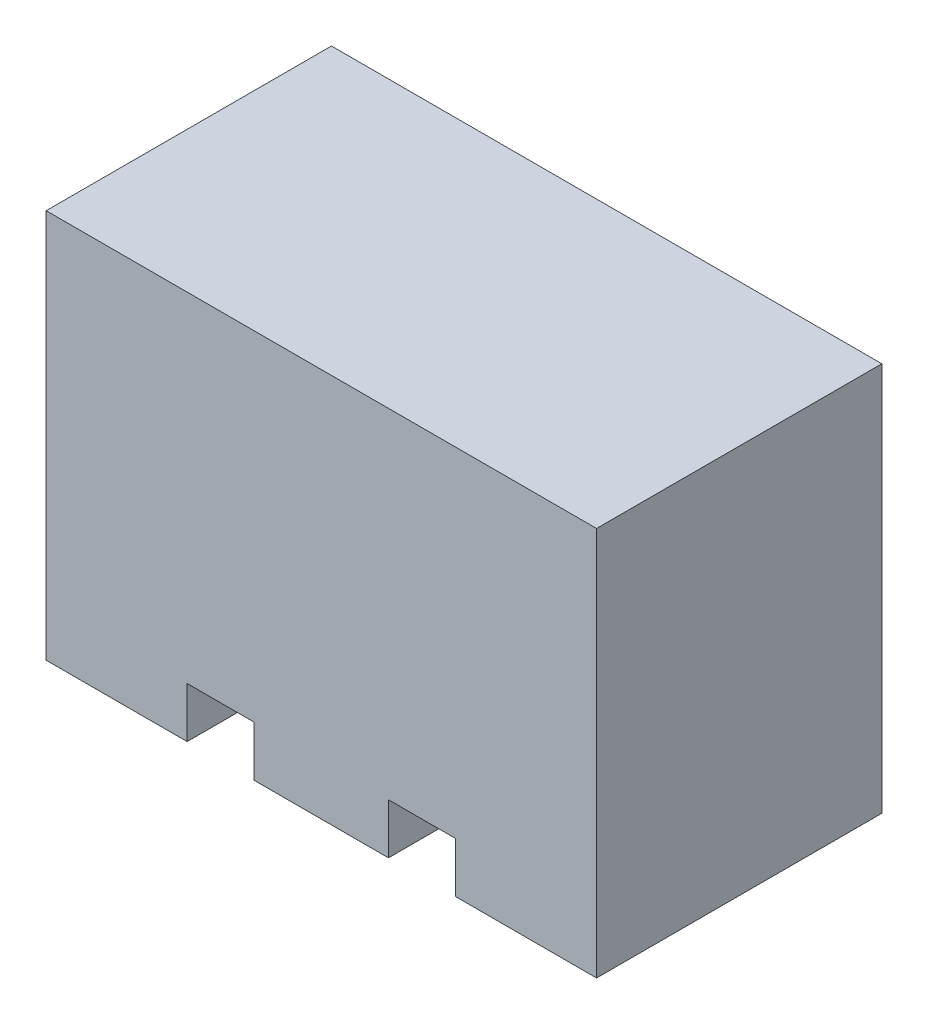
SolidWorks part; units mm, degrees
ref_plane "Přední rovina" through (0, 0, 0) normal (0, 0, 1) x (1, 0, 0)
ref_plane "Horní rovina" through (0, 0, 0) normal (0, 1, 0) x (1, 0, 0)
ref_plane "Pravá rovina" through (0, 0, 0) normal (1, 0, 0) x (0, 0, -1)
sketch "Skica1" plane through (0, 0, 0) normal (0, 0, 1) x (1, 0, 0)
  line L1 (0, 0) -> (16.4, 0)
  line L2 (0, 0) -> (0, 11.6)
  line L3 (0, 11.6) -> (16.4, 11.6)
  line L4 (16.4, 0) -> (16.4, 11.6)
  dimension "D1" = 16.4
  dimension "D2" = 11.6
extrude "Přidat vysunutím1" add sketch "Skica1" along normal blind 8.5
sketch "Skica2" plane through (0, 0, 8.5) normal (0, 0, 1) x (1, 0, 0)
  line L0 (0, 0) -> (16.4, 0) construction
  line L1 (4.2, 0) -> (6.2, 0)
  line L2 (4.2, 0) -> (4.2, 1.5)
  line L3 (4.2, 1.5) -> (6.2, 1.5)
  line L4 (6.2, 0) -> (6.2, 1.5)
  line L6 (10.2, 0) -> (12.2, 0)
  line L7 (10.2, 0) -> (10.2, 1.5)
  line L8 (10.2, 1.5) -> (12.2, 1.5)
  line L9 (12.2, 0) -> (12.2, 1.5)
  line L10 (6.2, 1.5) -> (10.2, 1.5)
  point P10 (8.2, 0)
  point P11 (8.2, 1.5)
  line M10 (0, 0) -> (16.4, 0)
  dimension "D1" = 4
  dimension "D2" = 2
  dimension "D3" = 2
  dimension "D5" = 1.5
extrude "Odebrat vysunutím1" cut sketch "Skica2" against normal through all contours L4 L3 L2 M10 | L9 L8 L7 M10 region at (5.2, 0.75, 8.5) region at (11.2, 0.75, 8.5)
